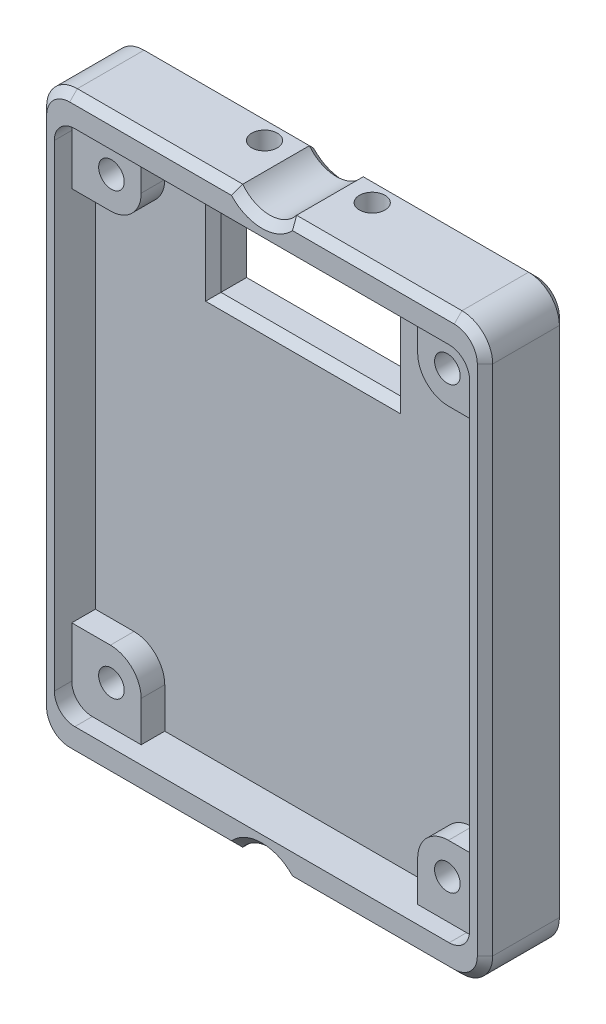
SolidWorks part; units mm, degrees
ref_plane "Front Plane" through (0, 0, 0) normal (0, 0, 1) x (1, 0, 0)
ref_plane "Top Plane" through (0, 0, 0) normal (0, 1, 0) x (1, 0, 0)
ref_plane "Right Plane" through (0, 0, 0) normal (1, 0, 0) x (0, 0, -1)
sketch "Sketch1" plane through (0, 0, 0) normal (0, 0, 1) x (1, 0, 0)
  line L0 (-23.25, 28.25) -> (-23.25, -28.25)
  line L1 (-20.25, 25.25) -> (20.25, 25.25)
  line L2 (-20.25, 25.25) -> (-20.25, -25.25)
  line L3 (-20.25, -25.25) -> (20.25, -25.25)
  line L4 (20.25, 25.25) -> (20.25, -25.25)
  line L5 (-20.25, 25.25) -> (20.25, -25.25) construction
  line L6 (-20.25, -25.25) -> (20.25, 25.25) construction
  line L7 (-23.25, -28.25) -> (23.25, -28.25)
  line L8 (23.25, 28.25) -> (23.25, -28.25)
  line L9 (-23.25, 28.25) -> (23.25, 28.25)
  point P0 (0, 0)
  dimension "D1" = 50.5
  dimension "D2" = 40.5
  dimension "D3" = 3
extrude "Boss-Extrude1" add sketch "Sketch1" along normal blind 4
sketch "Sketch2" plane through (0, 0, 0) normal (0, 0, -1) x (-1, 0, 0)
  line L1 (-23.25, 28.25) -> (23.25, 28.25)
  line L2 (-23.25, 28.25) -> (-23.25, -28.25)
  line L3 (-23.25, -28.25) -> (23.25, -28.25)
  line L4 (23.25, 28.25) -> (23.25, -28.25)
extrude "Boss-Extrude2" add sketch "Sketch2" along normal blind 4
sketch "Sketch3" plane through (0, 0, 0) normal (0, 0, 1) x (1, 0, 0)
  line L0 (0, 0) -> (0, 30.8352) construction
  line L1 (0, 0) -> (-31.9704, 0) construction
  line L2 (-20.25, 25.25) -> (-20.25, 18.3322)
  line L3 (-20.25, 25.25) -> (-20.25, -25.25) construction
  line L4 (-20.25, 18.3322) -> (-13.4806, 18.3322)
  line L5 (-13.4806, 18.3322) -> (-13.4806, 25.25)
  line L6 (20.25, 25.25) -> (-20.25, 25.25) construction
  line L7 (-13.4806, 25.25) -> (-20.25, 25.25)
  line L8 (13.4806, 25.25) -> (20.25, 25.25)
  line L9 (13.4806, 18.3322) -> (13.4806, 25.25)
  line L10 (20.25, 18.3322) -> (13.4806, 18.3322)
  line L11 (20.25, 25.25) -> (20.25, 18.3322)
  line L12 (20.25, -25.25) -> (20.25, -18.3322)
  line L13 (20.25, -18.3322) -> (13.4806, -18.3322)
  line L14 (13.4806, -18.3322) -> (13.4806, -25.25)
  line L15 (13.4806, -25.25) -> (20.25, -25.25)
  line L16 (-13.4806, -25.25) -> (-20.25, -25.25)
  line L17 (-13.4806, -18.3322) -> (-13.4806, -25.25)
  line L18 (-20.25, -18.3322) -> (-13.4806, -18.3322)
  line L19 (-20.25, -25.25) -> (-20.25, -18.3322)
  circle A0 centre (-16.38, 21.46) radius 1.25
  circle A1 centre (16.38, 21.46) radius 1.25
  circle A2 centre (16.38, -21.46) radius 1.25
  circle A3 centre (-16.38, -21.46) radius 1.25
  dimension "D3" = 2.5
  dimension "D1" = 21.46
  dimension "D2" = 16.38
extrude "Boss-Extrude3" add sketch "Sketch3" along normal blind 2.3
fillet "Fillet1" radius 3 4 edges at (13.4806, -18.3322, 1.15) (-13.4806, -18.3322, 1.15) (13.4806, 18.3322, 1.15) (-13.4806, 18.3322, 1.15)
sketch "Sketch4" plane through (0, 0, 0) normal (0, 0, 1) x (1, 0, 0)
  line L0 (20.25, 25.25) -> (-20.25, 25.25) construction
  line L1 (-8.75, 23.8) -> (8.75, 23.8)
  line L2 (-8.75, 23.8) -> (-8.75, 13.8)
  line L3 (-8.75, 13.8) -> (8.75, 13.8)
  line L4 (8.75, 23.8) -> (8.75, 13.8)
  point P4 (0, 13.8)
  dimension "D1" = 10
  dimension "D2" = 1.45
  dimension "D3" = 17.5
extrude "Cut-Extrude1" cut sketch "Sketch4" against normal through all
sketch "Sketch5" plane through (0, 0, -4) normal (0, 0, -1) x (-1, 0, 0)
  line L0 (-29.5901, 0) -> (35.962, 0) construction
  line L1 (-23.25, 28.25) -> (-23.25, 28)
  line L2 (23.25, 28.25) -> (-23.25, 28.25) construction
  line L3 (-23.25, 28) -> (-2.6249, 28)
  line L4 (0, 42.4173) -> (0, 14.6256) construction
  line L5 (23.25, 28) -> (2.6249, 28)
  line L6 (23.25, 28.25) -> (23.25, 28)
  line L7 (-23.25, 28.25) -> (23.25, 28.25)
  line L8 (-23.25, -28.25) -> (23.25, -28.25)
  line L9 (23.25, -28.25) -> (23.25, -28)
  line L10 (23.25, -28) -> (2.6249, -28)
  line L11 (-23.25, -28) -> (-2.6249, -28)
  line L12 (-23.25, -28.25) -> (-23.25, -28)
  line L13 (-23.25, 28.25) -> (-23.25, -28.25) construction
  arc A0 (-2.6249, 28) -> (2.6249, 28) centre (0, 30) ccw
  arc A1 (-2.6249, -28) -> (2.6249, -28) centre (0, -30) cw
  dimension "D1" = 6.6
  dimension "D2" = 2
  dimension "D3" = 60
extrude "Cut-Extrude2" cut sketch "Sketch5" against normal through all
sketch "Sketch6" plane through (0, 0, 4) normal (0, 0, 1) x (1, 0, 0)
  line L0 (-23.25, -28) -> (-2.6249, -28) construction
  line L1 (-23.25, 28) -> (-21.75, 28)
  line L2 (-23.25, 28) -> (-23.25, -28)
  line L3 (-23.25, -28) -> (-21.75, -28)
  line L4 (-21.75, 28) -> (-21.75, -28)
  line L5 (0, 0) -> (0, 31.5361) construction
  line L6 (21.75, 28) -> (21.75, -28)
  line L7 (23.25, -28) -> (21.75, -28)
  line L8 (23.25, 28) -> (23.25, -28)
  line L9 (23.25, 28) -> (21.75, 28)
  dimension "D1" = 1.5
extrude "Cut-Extrude3" cut sketch "Sketch6" against normal through all
sketch "Sketch7" plane through (0, 28, 0) normal (0, 1, 0) x (1, 0, 0)
  line L0 (-5.25, 1.5) -> (5.25, 1.5) construction
  line L1 (2.6249, 4) -> (-2.6249, 4) construction
  circle A0 centre (-5.25, 1.5) radius 1.25
  circle A1 centre (5.25, 1.5) radius 1.25
  point P4 (0, 1.5)
  dimension "D1" = 2.5
  dimension "D2" = 10.5
  dimension "D3" = 2.5
extrude "Cut-Extrude4" cut sketch "Sketch7" against normal blind 10
mirror "Mirror1" about plane through (0, 0, 0) normal (0, 1, 0) of "Cut-Extrude4"
fillet "Fillet2" radius 3 4 edges at (21.75, -28, 0) (-21.75, -28, 0) (-21.75, 28, 0) (21.75, 28, 0)
chamfer "Chamfer1" distance 0.75 angle 45 32 edges at (0, -26.7, 4) (0, 26.7, 4) (-10.6874, -28, 4) (-10.6874, 28, 4) (-20.8713, -27.1213, 4) (-20.8713, 27.1213, 4) (-21.75, 0, 4) (10.6874, 28, 4) (10.6874, -28, 4) (20.8713, 27.1213, 4) (20.8713, -27.1213, 4) (21.75, 0, 4) (0, 23.8, 0) (-8.75, 18.8, 0) (8.75, 18.8, 0) (0, 13.8, 0) (0, 26.7, -4) (8.75, 18.8, -4) (0, 13.8, -4) (-8.75, 18.8, -4) (0, 23.8, -4) (-10.6874, 28, -4) (10.6874, 28, -4) (-20.8713, 27.1213, -4) (20.8713, 27.1213, -4) (-21.75, 0, -4) (21.75, 0, -4) (-20.8713, -27.1213, -4) (20.8713, -27.1213, -4) (-10.6874, -28, -4) (0, -26.7, -4) (10.6874, -28, -4)
fillet "Fillet3" radius 2 4 edges at (-20.25, -25.25, 3.15) (20.25, -25.25, 3.15) (20.25, 25.25, 3.15) (-20.25, 25.25, 3.15)
sketch "Sketch8" plane through (0, 0, 2.3) normal (0, 0, 1) x (1, 0, 0)
  circle A0 centre (-16.38, 21.46) radius 1.25
  circle A1 centre (16.38, 21.46) radius 1.25
  circle A2 centre (16.38, -21.46) radius 1.25
  circle A3 centre (-16.38, -21.46) radius 1.25
  circle A4 centre (-16.38, 21.46) radius 1.25 construction
extrude "Cut-Extrude5" cut sketch "Sketch8" against normal through all
sketch "Sketch9" plane through (0, 0, -4) normal (0, 0, -1) x (-1, 0, 0)
  line L0 (0, 11.4111) -> (0, -15.9064) construction
  line L1 (-16.7591, 6.048) -> (-6.4216, 6.048)
  line L2 (-13.0037, 4.548) -> (-6.4216, 4.548)
  line L3 (-16.7591, 6.048) -> (0, -9.881)
  line L4 (-13.0037, 4.548) -> (0, -7.8115)
  line L5 (-4.0368, 5.298) -> (-12.2473, 5.298) construction
  line L6 (13.0037, 4.548) -> (0, -7.8115)
  line L7 (16.7591, 6.048) -> (0, -9.881)
  line L8 (13.0037, 4.548) -> (6.4216, 4.548)
  line L9 (16.7591, 6.048) -> (6.4216, 6.048)
  arc A0 (-6.4216, 4.548) -> (-6.4216, 6.048) centre (-4.0368, 5.298) ccw
  arc A1 (6.4216, 4.548) -> (6.4216, 6.048) centre (4.0368, 5.298) cw
  point P4 (0, -10.7426)
  point P9 (-10.6467, 4.455)
  point P11 (-3.6329, 5.074)
  point P14 (0, -7.8115)
  point P20 (0, -8.8937)
  point P21 (-4.0368, 5.3634)
  point P22 (-16.7591, 6.048)
  dimension "D1" = 5
  dimension "D2" = 1.5
  dimension "D3" = 1.5
extrude "Cut-Extrude6" cut sketch "Sketch9" against normal blind 1
